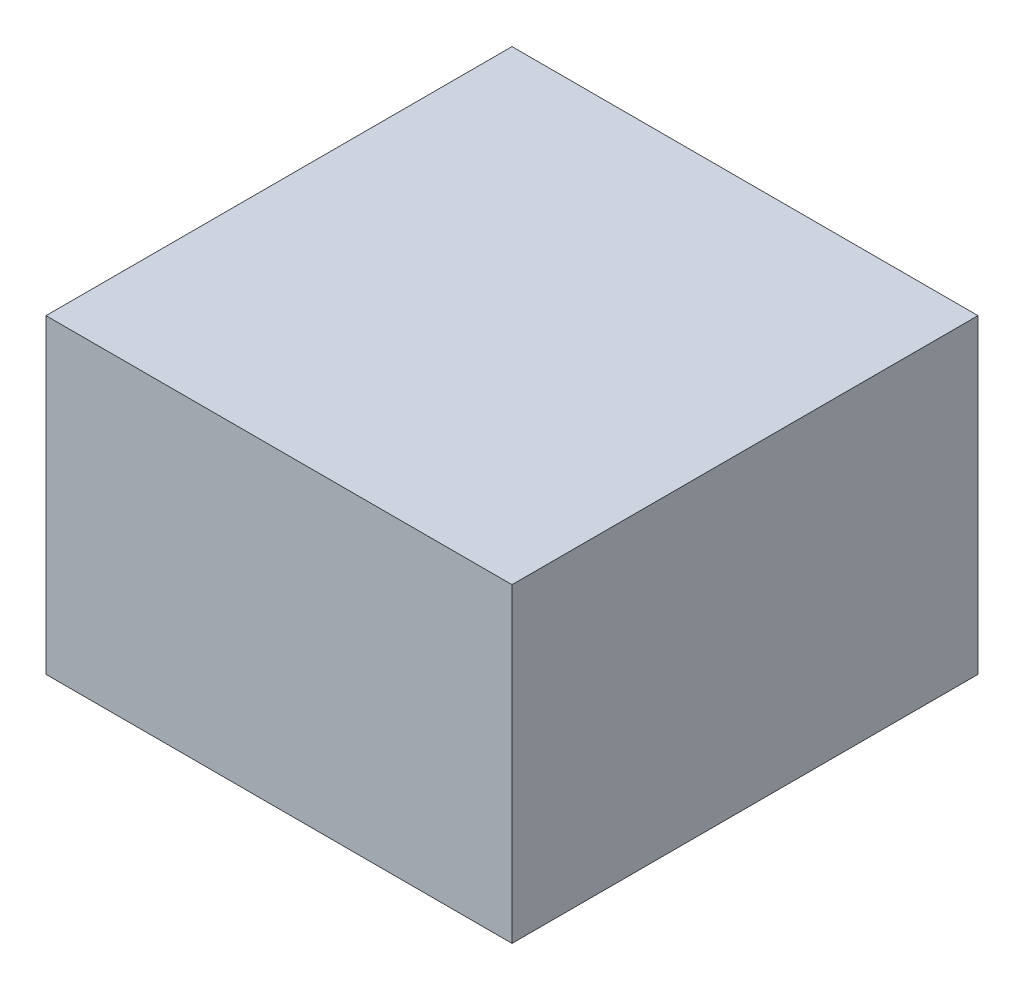
SolidWorks part; units mm, degrees
ref_plane "Front Plane" through (0, 0, 0) normal (0, 0, 1) x (1, 0, 0)
ref_plane "Top Plane" through (0, 0, 0) normal (0, 1, 0) x (1, 0, 0)
ref_plane "Right Plane" through (0, 0, 0) normal (1, 0, 0) x (0, 0, -1)
sketch "Sketch1" plane through (0, 0, 0) normal (0, 1, 0) x (1, 0, 0)
  line L1 (-37.5, 75) -> (37.5, 75)
  line L2 (-37.5, 75) -> (-37.5, 0)
  line L3 (-37.5, 0) -> (37.5, 0)
  line L4 (37.5, 75) -> (37.5, 0)
  point P4 (0, 0)
  dimension "D1" = 75
  dimension "D2" = 75
extrude "Boss-Extrude1" add sketch "Sketch1" along normal blind 50
